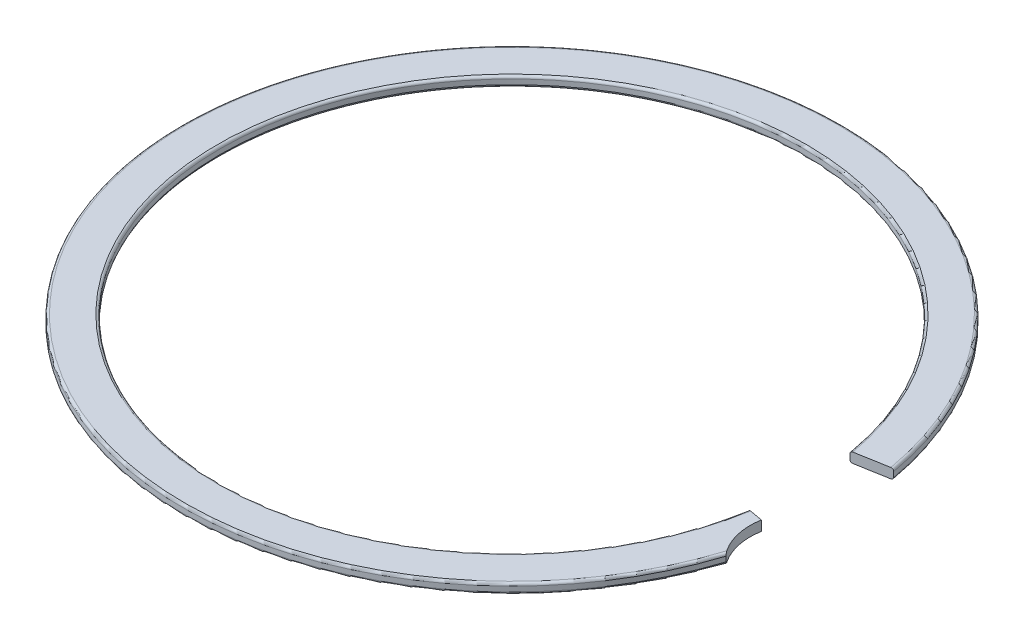
SolidWorks part; units mm, degrees
material "Cast Alloy Steel"
ref_plane "Front Plane" through (0, 0, 0) normal (0, 0, 1) x (1, 0, 0)
ref_plane "Top Plane" through (0, 0, 0) normal (0, 1, 0) x (1, 0, 0)
ref_plane "Right Plane" through (0, 0, 0) normal (1, 0, 0) x (0, 0, -1)
sketch "Sketch1" plane through (0, 0, 0) normal (0, 0, 1) x (1, 0, 0)
  line L0 (23.1267, 0.1969) -> (23.1267, -0.1969)
  line L1 (23.3236, -0.3937) -> (25.9271, -0.3937)
  line L2 (26.1239, -0.1969) -> (26.1239, 0.1969)
  line L3 (25.9271, 0.3937) -> (23.3236, 0.3937)
  line L4 (0, -1270) -> (0, 1270) construction
  arc A0 (23.1267, -0.1969) -> (23.3236, -0.3937) centre (23.3235, -0.1969) ccw
  arc A1 (25.9271, -0.3937) -> (26.1239, -0.1969) centre (25.9271, -0.1969) ccw
  arc A2 (26.1239, 0.1969) -> (25.9271, 0.3937) centre (25.9271, 0.1969) ccw
  arc A3 (23.3236, 0.3937) -> (23.1267, 0.1969) centre (23.3235, 0.1969) ccw
revolve "Revolve1" add sketch "Sketch1" angle 360 about L4 reverse direction yes
sketch "Sketch2" plane through (0, 0, 0) normal (0, 1, 0) x (1, 0, 0)
  line L0 (0, 0) -> (24.0052, -4.2328)
  line L1 (28.2997, 4.99) -> (0, 0)
  arc A0 (24.0052, -4.2328) -> (27.1083, -9.535) centre (28.6787, -5.0568) ccw
  arc A1 (27.1083, -9.535) -> (28.2997, 4.99) centre (0, 0) ccw
extrude "Cut-Extrude1" cut sketch "Sketch2" along normal blind 0.7874 and the other way blind 0.7874
ref_axis "Axis1" through (0, 0.4471, 0) along (0, -1, 0)
